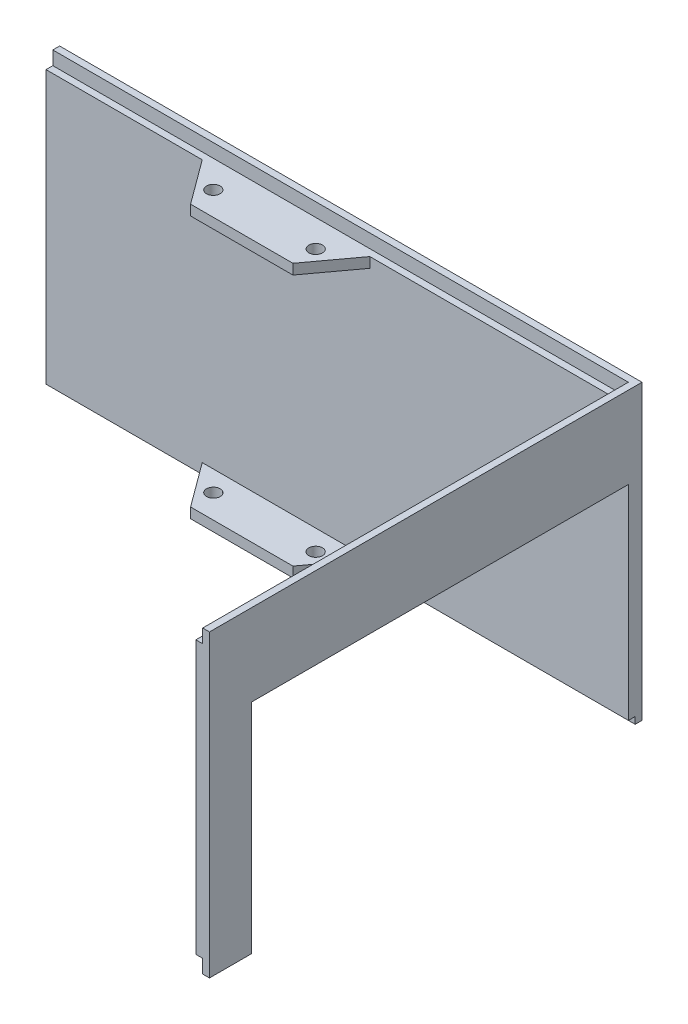
SolidWorks part; units mm, degrees
material "PLA (general purpose)"
ref_plane "Alzado" through (0, 0, 0) normal (0, 0, 1) x (1, 0, 0)
ref_plane "Planta" through (0, 0, 0) normal (0, 1, 0) x (1, 0, 0)
ref_plane "Vista lateral" through (0, 0, 0) normal (1, 0, 0) x (0, 0, -1)
sketch "Croquis1" plane through (0, 0, 0) normal (0, 0, 1) x (1, 0, 0)
  line L1 (85.5, -43) -> (-85.5, -43)
  line L2 (85.5, -43) -> (85.5, 43)
  line L3 (85.5, 43) -> (-85.5, 43)
  line L4 (-85.5, -43) -> (-85.5, 43)
  line L5 (85.5, -43) -> (-85.5, 43) construction
  line L6 (85.5, 43) -> (-85.5, -43) construction
  line L7 (-85.5, 39) -> (85.5, 39)
  line L8 (-85.5, 39) -> (-85.5, 43)
  line L9 (-85.5, 43) -> (85.5, 43)
  line L10 (85.5, 39) -> (85.5, 43)
  line L11 (-85.5, 39) -> (85.5, 43) construction
  line L12 (-85.5, 43) -> (85.5, 39) construction
  line L13 (-85.5, -41) -> (85.5, -41)
  line L14 (-85.5, -41) -> (-85.5, -43)
  line L15 (-85.5, -43) -> (85.5, -43)
  line L16 (85.5, -41) -> (85.5, -43)
  line L17 (-85.5, -41) -> (85.5, -43) construction
  line L18 (-85.5, -43) -> (85.5, -41) construction
  point P0 (0, 0)
  point P6 (0, 41)
  point P7 (0, -42)
  dimension "D1" = 171
  dimension "D2" = 86
  dimension "D3" = 4
  dimension "D4" = 2
extrude "Saliente-Extruir1" add sketch "Croquis1" along normal blind 4 contours L4 L13 L2 L7 region at (0, -1, 0)
extrude "Saliente-Extruir2" add sketch "Croquis1<3>" along normal blind 2 contours L4 L7 L2 L3 | L13 L4 L1 L2 region at (0, -42, 0) region at (0, 41, 0)
sketch "Croquis1<3>" plane through (0, 0, 0) normal (0, 0, 1) x (1, 0, 0) same geometry as "Croquis1"
sketch "Croquis2" plane through (85.5, 0, 0) normal (1, 0, 0) x (0, 0, -1)
  line L1 (-127, -41) -> (-114.644, -41)
  line L2 (-127, -41) -> (-127, 43)
  line L3 (-127, 43) -> (0, 43)
  line L4 (0, -41) -> (0, 43)
  line L5 (-127, -41) -> (0, 43) construction
  line L6 (-127, 43) -> (0, -41) construction
  line L7 (0, 39) -> (-127, 39)
  line L8 (0, 39) -> (0, 43)
  line L9 (0, 43) -> (-127, 43)
  line L10 (-127, 39) -> (-127, 43)
  line L11 (0, 39) -> (-127, 43) construction
  line L12 (0, 43) -> (-127, 39) construction
  line L13 (-114.644, 19) -> (0, 19)
  line L14 (-114.644, -45) -> (-127, -45)
  line L15 (-114.644, -45) -> (-114.644, 19)
  line L16 (-114.644, 39) -> (-127, 39)
  line L17 (-127, -45) -> (-127, 39)
  line L18 (-114.644, -45) -> (-127, 39) construction
  line L19 (-114.644, 39) -> (-127, -45) construction
  line L21 (-127, 19) -> (-127, 39)
  line L22 (-127, 39) -> (0, 39)
  line L23 (0, 19) -> (0, 39)
  line L24 (-127, 19) -> (0, 39) construction
  line L25 (-127, 39) -> (0, 19) construction
  point P0 (-63.5, 1)
  point P6 (-63.5, 41)
  point P7 (-120.822, -3)
  point P10 (-63.5, 29)
  line M17 (-2, 43) -> (-2, 39)
  line M18 (-2, 39) -> (-4, 39)
  line M19 (-4, 39) -> (-4, -41)
  dimension "D1" = 127
  dimension "D2" = 84
  dimension "D3" = 4
  dimension "D4" = 84
  dimension "D5" = 28
  dimension "D6" = 29
  dimension "D7" = 19
  dimension "D8" = 12.356
  dimension "D9" = 10
  dimension "D10" = 4
extrude "Saliente-Extruir3" add sketch "Croquis2" against normal blind 4 contours L1 L15 L13 L7 L17 L2 M19 region at (85.5, 19.7369, 78.3113)
extrude "Saliente-Extruir4" add sketch "Croquis2<3>" against normal blind 2 contours L7 L3 L2 M18 M17 | L17 L14 L15 L1 region at (85.5, -43, 120.822) region at (85.5, 41, 64.5)
sketch "Croquis2<3>" plane through (85.5, 0, 0) normal (1, 0, 0) x (0, 0, -1) same geometry as "Croquis2"
sketch "Croquis3" plane through (0, -41, 0) normal (0, -1, 0) x (1, 0, 0)
  line L0 (85.5, 2) -> (-85.5, 2) construction
  line L1 (-30.05, 17) -> (0, 17)
  line L2 (-30.05, 17) -> (-30.05, 2)
  line L3 (-30.05, 2) -> (0, 2)
  line L4 (0, 17) -> (0, 2)
  line L5 (-30.05, 17) -> (0, 2) construction
  line L6 (-30.05, 2) -> (0, 17) construction
  line L7 (81.5, 114.644) -> (81.5, 4) construction
  line L8 (-30.05, 17) -> (-41.1009, 2)
  line L9 (-85.5, 2) -> (85.5, 2) construction
  line L10 (-41.1009, 2) -> (-30.05, 2)
  line L11 (0, 17) -> (11.0509, 2)
  line L12 (11.0509, 2) -> (0, 2)
  point P0 (-15.025, 9.5)
  line M8 (85.5, 4) -> (-85.5, 4)
  dimension "D1" = 81.5
  dimension "D2" = 30.05
  dimension "D3" = 15
  dimension "D4" = 53.62
  dimension "D5" = 53.62
extrude "Saliente-Extruir5" add sketch "Croquis3" against normal blind 3 contours L11 L4 M8 | L2 L8 M8 | L4 L1 L2 M8 region at (-15.025, -41, 10.5) region at (-33.2425, -41, 8.3333) region at (3.1925, -41, 8.3333)
sketch "Croquis4" plane through (0, -38, 0) normal (0, 1, 0) x (1, 0, 0)
  line L0 (-85.5, -2) -> (83.5, -2) construction
  line L1 (83.5, -127) -> (83.5, -2) construction
  line L4 (83.5, -2) -> (-85.5, -2) construction
  circle A0 centre (-0.3, -10.02) radius 2
  circle A1 centre (-30.35, -10.02) radius 2
  dimension "D4" = 4
  dimension "D5" = 4
  dimension "D1" = 30.05
  dimension "D2" = 8.02
  dimension "D3" = 83.8
  dimension "D6" = 8.02
extrude "Cortar-Extruir1" cut sketch "Croquis4" against normal blind 3
ref_plane "Plano1" through (0, -1, 0) normal (0, -1, 0) x (-1, 0, 0)
mirror "Simetría1" about plane through (0, -1, 0) normal (0, -1, 0) of "Cortar-Extruir1", "Saliente-Extruir5"
